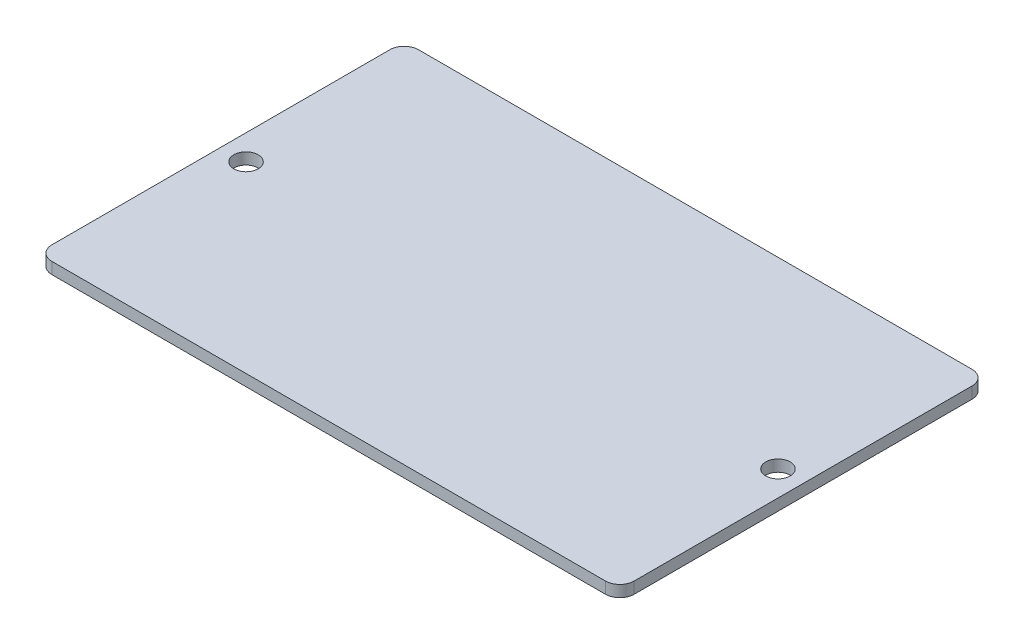
SolidWorks part; units mm, degrees
ref_plane "Front Plane" through (0, 0, 0) normal (0, 0, 1) x (1, 0, 0)
ref_plane "Top Plane" through (0, 0, 0) normal (0, 1, 0) x (1, 0, 0)
ref_plane "Right Plane" through (0, 0, 0) normal (1, 0, 0) x (0, 0, -1)
ref_axis "X" through (-88.99, 0, 0) along (1, 0, 0)
ref_axis "Y" through (0, 55, 0) along (0, -1, 0)
ref_axis "Z" through (0, 0, -88.99) along (0, 0, 1)
sketch "Sketch1" plane through (0, 0, 0) normal (0, 1, 0) x (1, 0, 0)
  line L0 (-37, 0) -> (37, 0) construction
  line L2 (-40.5, 25.5) -> (40.5, 25.5)
  line L3 (-40.5, 25.5) -> (-40.5, -25.5)
  line L4 (-40.5, -25.5) -> (40.5, -25.5)
  line L5 (40.5, 25.5) -> (40.5, -25.5)
  line L6 (-40.5, 25.5) -> (40.5, -25.5) construction
  line L7 (-40.5, -25.5) -> (40.5, 25.5) construction
  circle A0 centre (-37, 0) radius 1.7
  circle A1 centre (37, 0) radius 1.7
  point P4 (0, 0)
  point P6 (0, 0)
  dimension "D2" = 3.4
  dimension "D1" = 74
  dimension "D3" = 51
  dimension "D4" = 81
extrude "Boss-Extrude1" add sketch "Sketch1" along normal blind 1.6
fillet "Fillet1" radius 2 4 edges at (-40.5, 0.8, -25.5) (40.5, 0.8, -25.5) (40.5, 0.8, 25.5) (-40.5, 0.8, 25.5)
